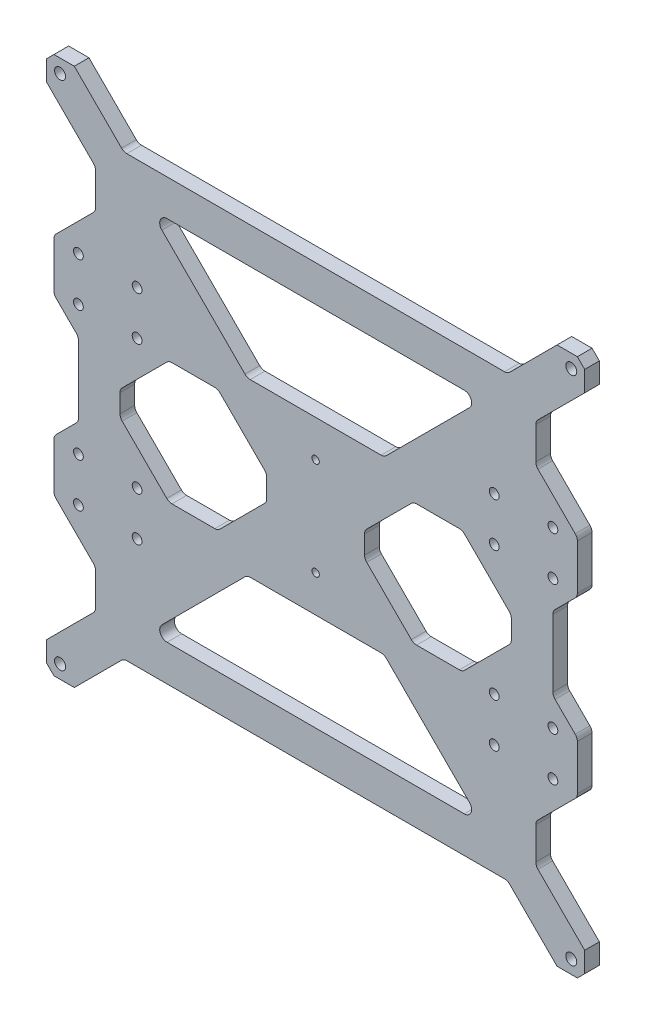
SolidWorks part; units mm, degrees
ref_plane "Plano frontal" through (0, 0, 0) normal (0, 0, 1) x (1, 0, 0)
ref_plane "Plano superior" through (0, 0, 0) normal (0, 1, 0) x (1, 0, 0)
ref_plane "Plano direito" through (0, 0, 0) normal (1, 0, 0) x (0, 0, -1)
sketch "Model" plane through (0, 0, 0) normal (0, 0, 1) x (1, 0, 0)
  line L0 (25.3498, 230.2402) -> (23.3498, 230.2402)
  line L1 (23.3498, 230.2402) -> (20.3498, 227.2402)
  line L2 (20.3498, 227.2402) -> (20.3498, 225.2402)
  line L3 (20.3498, 225.2402) -> (20.3498, 223.2402)
  line L4 (40.3498, 197.6839) -> (40.3498, 184.4828)
  line L5 (39.4711, 182.3615) -> (24.2285, 167.1189)
  line L6 (130.3498, 155.2402) -> (103.5924, 155.2402)
  line L7 (51.2285, 126.1189) -> (69.4711, 144.3615)
  line L8 (71.5924, 145.2402) -> (89.1071, 145.2402)
  line L9 (91.2285, 144.3615) -> (109.4711, 126.1189)
  line L10 (110.3498, 123.9976) -> (110.3498, 120.2402)
  line L11 (50.3498, 120.2402) -> (50.3498, 123.9976)
  line L12 (25.3498, 230.2402) -> (27.3498, 230.2402)
  line L13 (69.5924, 195.2402) -> (130.3498, 195.2402)
  line L14 (67.4711, 190.1189) -> (101.4711, 156.1189)
  line L15 (23.3498, 164.9976) -> (23.3498, 146.4969)
  line L16 (27.3498, 230.2402) -> (31.6635, 230.2402)
  line L17 (20.3498, 223.2402) -> (20.3498, 218.9265)
  line L18 (20.3498, 218.9265) -> (39.4711, 199.8052)
  line L19 (31.6635, 230.2402) -> (51.0065, 210.8972)
  line L20 (53.1278, 210.0186) -> (130.3498, 210.0186)
  line L21 (32.4711, 136.133) -> (24.2285, 144.3756)
  line L22 (33.3498, 134.0116) -> (33.3498, 120.2402)
  line L23 (235.3498, 230.2402) -> (237.3498, 230.2402)
  line L24 (237.3498, 230.2402) -> (240.3498, 227.2402)
  line L25 (240.3498, 227.2402) -> (240.3498, 225.2402)
  line L26 (240.3498, 225.2402) -> (240.3498, 223.2402)
  line L27 (220.3498, 197.6839) -> (220.3498, 184.4828)
  line L28 (221.2285, 182.3615) -> (236.4711, 167.1189)
  line L29 (130.3498, 155.2402) -> (157.1071, 155.2402)
  line L30 (209.4711, 126.1189) -> (191.2285, 144.3615)
  line L31 (189.1071, 145.2402) -> (171.5924, 145.2402)
  line L32 (169.4711, 144.3615) -> (151.2285, 126.1189)
  line L33 (150.3498, 123.9976) -> (150.3498, 120.2402)
  line L34 (210.3498, 120.2402) -> (210.3498, 123.9976)
  line L35 (235.3498, 230.2402) -> (233.3498, 230.2402)
  line L36 (191.1071, 195.2402) -> (130.3498, 195.2402)
  line L37 (193.2285, 190.1189) -> (159.2285, 156.1189)
  line L38 (237.3498, 164.9976) -> (237.3498, 146.4969)
  line L39 (233.3498, 230.2402) -> (229.0361, 230.2402)
  line L40 (240.3498, 223.2402) -> (240.3498, 218.9265)
  line L41 (240.3498, 218.9265) -> (221.2285, 199.8052)
  line L42 (229.0361, 230.2402) -> (209.6931, 210.8972)
  line L43 (207.5718, 210.0186) -> (130.3498, 210.0186)
  line L44 (228.2285, 136.133) -> (236.4711, 144.3756)
  line L45 (227.3498, 134.0116) -> (227.3498, 120.2402)
  line L46 (25.3498, 10.2402) -> (23.3498, 10.2402)
  line L47 (23.3498, 10.2402) -> (20.3498, 13.2402)
  line L48 (20.3498, 13.2402) -> (20.3498, 15.2402)
  line L49 (20.3498, 15.2402) -> (20.3498, 17.2402)
  line L50 (40.3498, 42.7966) -> (40.3498, 55.9976)
  line L51 (39.4711, 58.1189) -> (24.2285, 73.3615)
  line L52 (130.3498, 85.2402) -> (103.5924, 85.2402)
  line L53 (51.2285, 114.3615) -> (69.4711, 96.1189)
  line L54 (71.5924, 95.2402) -> (89.1071, 95.2402)
  line L55 (91.2285, 96.1189) -> (109.4711, 114.3615)
  line L56 (110.3498, 116.4828) -> (110.3498, 120.2402)
  line L57 (50.3498, 120.2402) -> (50.3498, 116.4828)
  line L58 (25.3498, 10.2402) -> (27.3498, 10.2402)
  line L59 (69.5924, 45.2402) -> (130.3498, 45.2402)
  line L60 (23.3498, 75.4828) -> (23.3498, 93.9835)
  line L61 (27.3498, 10.2402) -> (31.6635, 10.2402)
  line L62 (20.3498, 17.2402) -> (20.3498, 21.5539)
  line L63 (20.3498, 21.5539) -> (39.4711, 40.6752)
  line L64 (31.6635, 10.2402) -> (51.0065, 29.5832)
  line L65 (53.1278, 30.4618) -> (130.3498, 30.4618)
  line L66 (32.4711, 104.3475) -> (24.2285, 96.1048)
  line L67 (33.3498, 106.4688) -> (33.3498, 120.2402)
  line L68 (235.3498, 10.2402) -> (237.3498, 10.2402)
  line L69 (237.3498, 10.2402) -> (240.3498, 13.2402)
  line L70 (240.3498, 13.2402) -> (240.3498, 15.2402)
  line L71 (240.3498, 15.2402) -> (240.3498, 17.2402)
  line L72 (220.3498, 42.7966) -> (220.3498, 55.9976)
  line L73 (221.2285, 58.1189) -> (236.4711, 73.3615)
  line L74 (130.3498, 85.2402) -> (157.1071, 85.2402)
  line L75 (209.4711, 114.3615) -> (191.2285, 96.1189)
  line L76 (189.1071, 95.2402) -> (171.5924, 95.2402)
  line L77 (169.4711, 96.1189) -> (151.2285, 114.3615)
  line L78 (150.3498, 116.4828) -> (150.3498, 120.2402)
  line L79 (210.3498, 120.2402) -> (210.3498, 116.4828)
  line L80 (235.3498, 10.2402) -> (233.3498, 10.2402)
  line L81 (191.1071, 45.2402) -> (130.3498, 45.2402)
  line L82 (193.2285, 50.3615) -> (159.2285, 84.3615)
  line L83 (237.3498, 75.4828) -> (237.3498, 93.9835)
  line L84 (233.3498, 10.2402) -> (229.0361, 10.2402)
  line L85 (240.3498, 17.2402) -> (240.3498, 21.5539)
  line L86 (240.3498, 21.5539) -> (221.2285, 40.6752)
  line L87 (229.0361, 10.2402) -> (209.6931, 29.5832)
  line L88 (207.5718, 30.4618) -> (130.3498, 30.4618)
  line L89 (228.2285, 104.3475) -> (236.4711, 96.1048)
  line L90 (227.3498, 106.4688) -> (227.3498, 120.2402)
  line L91 (67.4711, 50.3615) -> (101.4711, 84.3615)
  arc A0 (39.4711, 182.3615) -> (40.3498, 184.4828) centre (37.3498, 184.4828) ccw
  arc A1 (24.2285, 167.1189) -> (23.3498, 164.9976) centre (26.3498, 164.9976) ccw
  arc A2 (101.4711, 156.1189) -> (103.5924, 155.2402) centre (103.5924, 158.2402) ccw
  arc A3 (71.5924, 145.2402) -> (69.4711, 144.3615) centre (71.5924, 142.2402) ccw
  arc A4 (91.2285, 144.3615) -> (89.1071, 145.2402) centre (89.1071, 142.2402) ccw
  arc A5 (110.3498, 123.9976) -> (109.4711, 126.1189) centre (107.3498, 123.9976) ccw
  arc A6 (51.2285, 126.1189) -> (50.3498, 123.9976) centre (53.3498, 123.9976) ccw
  arc A7 (69.5924, 195.2402) -> (67.4711, 190.1189) centre (69.5924, 192.2402) ccw
  arc A8 (23.3498, 146.4969) -> (24.2285, 144.3756) centre (26.3498, 146.4969) ccw
  circle A9 centre (25.8498, 224.7402) radius 2.25
  arc A10 (130.3498, 141.7402) -> (130.3498, 138.7402) centre (130.3498, 140.2402) ccw
  circle A11 centre (57.3498, 164.7472) radius 2
  circle A12 centre (57.3498, 146.7472) radius 2
  circle A13 centre (33.3498, 146.7472) radius 2
  circle A14 centre (33.3498, 164.7472) radius 2
  arc A15 (40.3498, 197.6839) -> (39.4711, 199.8052) centre (37.3498, 197.6839) ccw
  arc A16 (51.0065, 210.8972) -> (53.1278, 210.0186) centre (53.1278, 213.0186) ccw
  arc A17 (33.3498, 134.0116) -> (32.4711, 136.133) centre (30.3498, 134.0116) ccw
  arc A18 (220.3498, 184.4828) -> (221.2285, 182.3615) centre (223.3498, 184.4828) ccw
  arc A19 (237.3498, 164.9976) -> (236.4711, 167.1189) centre (234.3498, 164.9976) ccw
  arc A20 (157.1071, 155.2402) -> (159.2285, 156.1189) centre (157.1071, 158.2402) ccw
  arc A21 (191.2285, 144.3615) -> (189.1071, 145.2402) centre (189.1071, 142.2402) ccw
  arc A22 (171.5924, 145.2402) -> (169.4711, 144.3615) centre (171.5924, 142.2402) ccw
  arc A23 (151.2285, 126.1189) -> (150.3498, 123.9976) centre (153.3498, 123.9976) ccw
  arc A24 (210.3498, 123.9976) -> (209.4711, 126.1189) centre (207.3498, 123.9976) ccw
  arc A25 (193.2285, 190.1189) -> (191.1071, 195.2402) centre (191.1071, 192.2402) ccw
  arc A26 (236.4711, 144.3756) -> (237.3498, 146.4969) centre (234.3498, 146.4969) ccw
  circle A27 centre (234.8498, 224.7402) radius 2.25
  arc A28 (130.3498, 138.7402) -> (130.3498, 141.7402) centre (130.3498, 140.2402) ccw
  circle A29 centre (203.3498, 164.7472) radius 2
  circle A30 centre (203.3498, 146.7472) radius 2
  circle A31 centre (227.3498, 146.7472) radius 2
  circle A32 centre (227.3498, 164.7472) radius 2
  arc A33 (221.2285, 199.8052) -> (220.3498, 197.6839) centre (223.3498, 197.6839) ccw
  arc A34 (207.5718, 210.0186) -> (209.6931, 210.8972) centre (207.5718, 213.0186) ccw
  arc A35 (228.2285, 136.133) -> (227.3498, 134.0116) centre (230.3498, 134.0116) ccw
  arc A36 (40.3498, 55.9976) -> (39.4711, 58.1189) centre (37.3498, 55.9976) ccw
  arc A37 (23.3498, 75.4828) -> (24.2285, 73.3615) centre (26.3498, 75.4828) ccw
  arc A38 (103.5924, 85.2402) -> (101.4711, 84.3615) centre (103.5924, 82.2402) ccw
  arc A39 (69.4711, 96.1189) -> (71.5924, 95.2402) centre (71.5924, 98.2402) ccw
  arc A40 (89.1071, 95.2402) -> (91.2285, 96.1189) centre (89.1071, 98.2402) ccw
  arc A41 (109.4711, 114.3615) -> (110.3498, 116.4828) centre (107.3498, 116.4828) ccw
  arc A42 (50.3498, 116.4828) -> (51.2285, 114.3615) centre (53.3498, 116.4828) ccw
  arc A43 (67.4711, 50.3615) -> (69.5924, 45.2402) centre (69.5924, 48.2402) ccw
  arc A44 (24.2285, 96.1048) -> (23.3498, 93.9835) centre (26.3498, 93.9835) ccw
  circle A45 centre (25.8498, 15.7402) radius 2.25
  arc A46 (130.3498, 101.7402) -> (130.3498, 98.7402) centre (130.3498, 100.2402) ccw
  circle A47 centre (57.3498, 75.7332) radius 2
  circle A48 centre (57.3498, 93.7332) radius 2
  circle A49 centre (33.3498, 93.7332) radius 2
  circle A50 centre (33.3498, 75.7332) radius 2
  arc A51 (39.4711, 40.6752) -> (40.3498, 42.7966) centre (37.3498, 42.7966) ccw
  arc A52 (53.1278, 30.4618) -> (51.0065, 29.5832) centre (53.1278, 27.4618) ccw
  arc A53 (32.4711, 104.3475) -> (33.3498, 106.4688) centre (30.3498, 106.4688) ccw
  arc A54 (221.2285, 58.1189) -> (220.3498, 55.9976) centre (223.3498, 55.9976) ccw
  arc A55 (236.4711, 73.3615) -> (237.3498, 75.4828) centre (234.3498, 75.4828) ccw
  arc A56 (159.2285, 84.3615) -> (157.1071, 85.2402) centre (157.1071, 82.2402) ccw
  arc A57 (189.1071, 95.2402) -> (191.2285, 96.1189) centre (189.1071, 98.2402) ccw
  arc A58 (169.4711, 96.1189) -> (171.5924, 95.2402) centre (171.5924, 98.2402) ccw
  arc A59 (150.3498, 116.4828) -> (151.2285, 114.3615) centre (153.3498, 116.4828) ccw
  arc A60 (209.4711, 114.3615) -> (210.3498, 116.4828) centre (207.3498, 116.4828) ccw
  arc A61 (191.1071, 45.2402) -> (193.2285, 50.3615) centre (191.1071, 48.2402) ccw
  arc A62 (237.3498, 93.9835) -> (236.4711, 96.1048) centre (234.3498, 93.9835) ccw
  circle A63 centre (234.8498, 15.7402) radius 2.25
  arc A64 (130.3498, 98.7402) -> (130.3498, 101.7402) centre (130.3498, 100.2402) ccw
  circle A65 centre (203.3498, 75.7332) radius 2
  circle A66 centre (203.3498, 93.7332) radius 2
  circle A67 centre (227.3498, 93.7332) radius 2
  circle A68 centre (227.3498, 75.7332) radius 2
  arc A69 (220.3498, 42.7966) -> (221.2285, 40.6752) centre (223.3498, 42.7966) ccw
  arc A70 (209.6931, 29.5832) -> (207.5718, 30.4618) centre (207.5718, 27.4618) ccw
  arc A71 (227.3498, 106.4688) -> (228.2285, 104.3475) centre (230.3498, 106.4688) ccw
extrude "Ressalto-extrusão1" add sketch "Model" along normal blind 6
